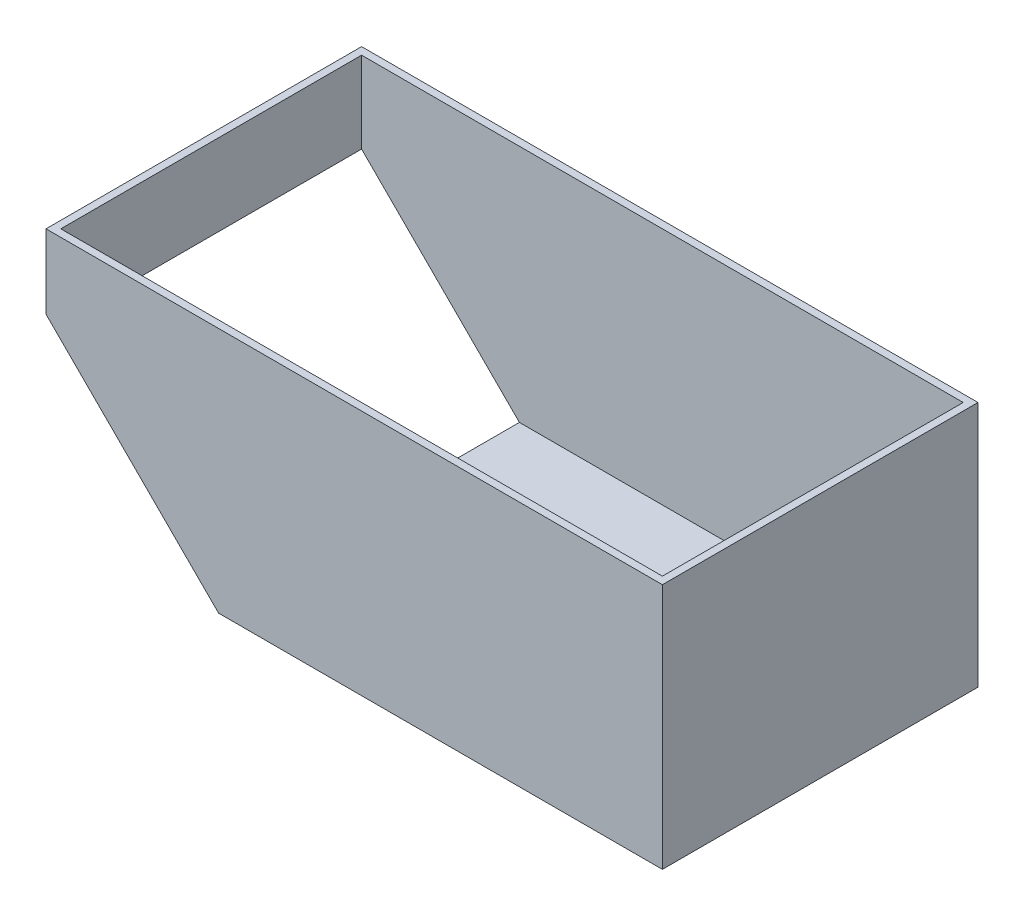
SolidWorks part; units mm, degrees
ref_plane "Front Plane" through (0, 0, 0) normal (0, 0, 1) x (1, 0, 0)
ref_plane "Top Plane" through (0, 0, 0) normal (0, 1, 0) x (1, 0, 0)
ref_plane "Right Plane" through (0, 0, 0) normal (1, 0, 0) x (0, 0, -1)
sketch "Sketch1" plane through (0, 0, 0) normal (0, 1, 0) x (1, 0, 0)
  line L1 (0, 0) -> (250, 0)
  line L2 (0, 0) -> (0, 128)
  line L3 (0, 128) -> (250, 128)
  line L4 (250, 0) -> (250, 128)
  dimension "D1" = 250
  dimension "D2" = 128
extrude "Boss-Extrude1" add sketch "Sketch1" along normal blind 3
sketch "Sketch2" plane through (0, 0, 0) normal (0, 1, 0) x (1, 0, 0)
  line L0 (247, 3) -> (247, 125)
  line L1 (250, 0) -> (0, 0)
  line L2 (250, 0) -> (250, 128)
  line L3 (250, 128) -> (0, 128)
  line L4 (0, 0) -> (0, 128)
  line L5 (247, 125) -> (3, 125)
  line L6 (3, 3) -> (3, 125)
  line L7 (247, 3) -> (3, 3)
  dimension "D1" = 3
extrude "Boss-Extrude2" add sketch "Sketch2" along normal blind 100
sketch "Sketch3" plane through (0, 0, 0) normal (0, 0, 1) x (1, 0, 0)
  line L0 (0, 70) -> (70, 0)
  line L1 (0, 0) -> (250, 0) construction
  line L2 (70, 0) -> (0, 0)
  line L3 (0, 0) -> (0, 70)
  line L4 (0, 100) -> (0, 0) construction
  dimension "D1" = 45
  dimension "D2" = 30
extrude "Cut-Extrude1" cut sketch "Sketch3" against normal through all both and the other way through all
